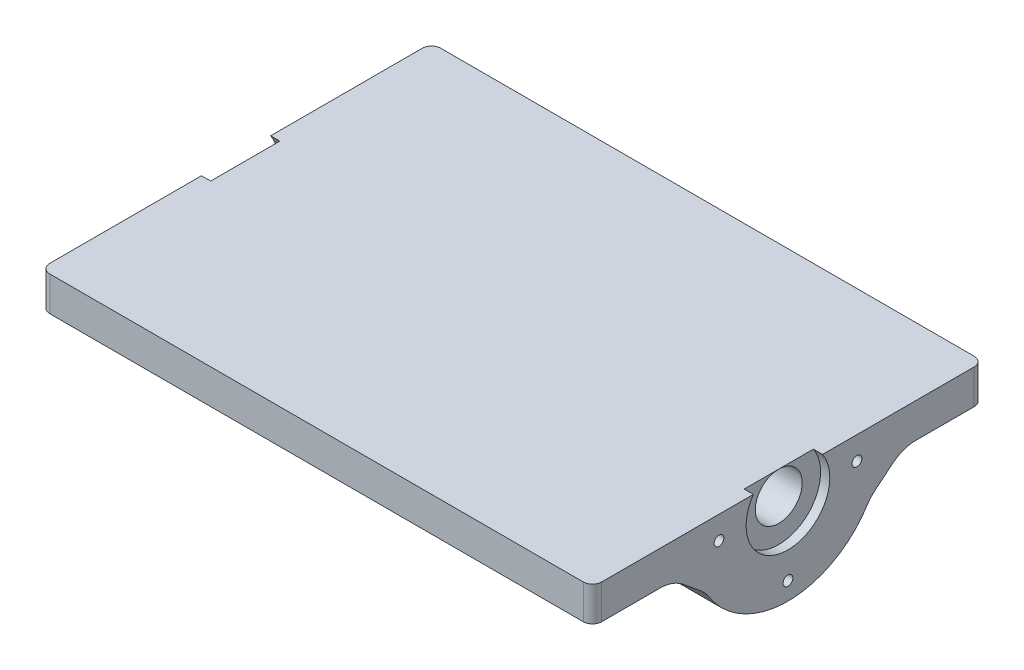
SolidWorks part; units mm, degrees
material "Copper"
ref_plane "Front Plane" through (0, 0, 0) normal (0, 0, 1) x (1, 0, 0)
ref_plane "Top Plane" through (0, 0, 0) normal (0, 1, 0) x (1, 0, 0)
ref_plane "Right Plane" through (0, 0, 0) normal (1, 0, 0) x (0, 0, -1)
sketch "Sketch1" plane through (0, 0, 0) normal (0, 0, 1) x (1, 0, 0)
  line L1 (0, 0) -> (-152.4, 0)
  line L2 (0, 0) -> (0, -38.1)
  line L3 (0, -38.1) -> (-152.4, -38.1)
  line L4 (-152.4, 0) -> (-152.4, -38.1)
  dimension "D1" = 152.4
  dimension "D2" = 38.1
extrude "Boss-Extrude1" add sketch "Sketch1" along normal blind 107.95
sketch "Sketch2" plane through (0, 0, 0) normal (1, 0, 0) x (0, 0, -1)
  line L0 (-53.975, 0) -> (-53.975, -38.1)
  line L1 (-107.95, 0) -> (0, 0) construction
  line L2 (-107.95, -38.1) -> (0, -38.1) construction
  circle A0 centre (-73.025, -6.35) radius 1.3525
  circle A1 centre (-34.925, -6.35) radius 1.3526
  circle A2 centre (-53.975, -25.4) radius 1.3525
  dimension "D1" = 2.7051
  dimension "D2" = 2.7051
  dimension "D8" = 2.7051
  dimension "D3" = 31.75
  dimension "D4" = 31.75
  dimension "D5" = 19.05
  dimension "D6" = 19.05
  dimension "D7" = 19.05
extrude "Cut-Extrude1" cut sketch "Sketch2" against normal blind 152.4 contours A0 | L0 A2 | A1
sketch "Sketch3" plane through (0, 0, 0) normal (1, 0, 0) x (0, 0, -1)
  line L0 (-53.975, 0) -> (-53.975, -38.1) construction
  line L1 (-107.95, 0) -> (0, 0) construction
  line L2 (-107.95, -38.1) -> (0, -38.1) construction
  circle A0 centre (-53.975, -6.5024) radius 6.477
  dimension "D1" = 12.954
  dimension "D2" = 31.5976
extrude "Cut-Extrude4" cut sketch "Sketch3" against normal blind 154.686
sketch "Sketch4" plane through (0, 0, 0) normal (1, 0, 0) x (0, 0, -1)
  circle A0 centre (-53.975, -6.5024) radius 11.557
  dimension "D1" = 23.114
extrude "Cut-Extrude5" cut sketch "Sketch4" against normal blind 2.54
ref_plane "Plane1" through (-76.2, 0, 0) normal (1, 0, 0) x (0, 0, -1)
mirror "Mirror1" about plane through (-76.2, 0, 0) normal (1, 0, 0) of "Cut-Extrude5"
sketch "Sketch5" plane through (0, 0, 0) normal (1, 0, 0) x (0, 0, -1)
  line L0 (-107.95, -9.525) -> (-79.375, -9.525)
  line L1 (-107.95, -38.1) -> (-107.95, 0) construction
  line L2 (-28.575, -9.525) -> (0, -9.525)
  line L3 (0, -38.1) -> (0, 0) construction
  line L4 (0, -9.525) -> (0, -59.7545)
  line L5 (0, -59.7545) -> (-107.95, -59.7545)
  line L6 (-107.95, -9.525) -> (-107.95, -59.7545)
  line L7 (-44.4208, 0) -> (0, 0) construction
  line L8 (-107.95, 0) -> (-63.5292, 0) construction
  arc A0 (-79.375, -9.525) -> (-28.575, -9.525) centre (-53.975, -4.4197) ccw
  dimension "D1" = 28.575
  dimension "D5" = 25.908
  dimension "D2" = 28.575
  dimension "D3" = 9.525
  dimension "D4" = 9.525
extrude "Cut-Extrude6" cut sketch "Sketch5" against normal blind 152.4
chamfer "Chamfer1" distance 6.35 2 edges at (-76.2, -9.525, 79.375) (-76.2, -9.525, 28.575)
fillet "Fillet1" radius 10 4 edges at (-76.2, -9.525, 85.725) (-76.2, -16.9616, 76.6449) (-76.2, -16.9616, 31.3051) (-76.2, -9.525, 22.225)
fillet "Fillet2" radius 2.54 4 edges at (0, -4.7625, 107.95) (-152.4, -4.7625, 107.95) (-152.4, -4.7625, 0) (0, -4.7625, 0)
